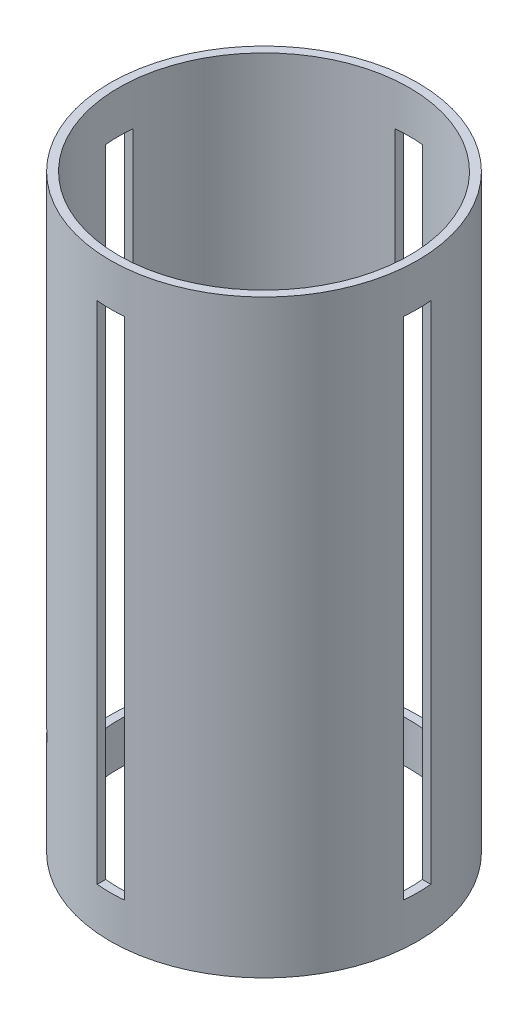
SolidWorks part; units mm, degrees
ref_plane "Front Plane" through (0, 0, 0) normal (0, 0, 1) x (1, 0, 0)
ref_plane "Top Plane" through (0, 0, 0) normal (0, 1, 0) x (1, 0, 0)
ref_plane "Right Plane" through (0, 0, 0) normal (1, 0, 0) x (0, 0, -1)
ref_axis "Axis1" through (0, 125, 0) along (0, -1, 0)
sketch "Sketch1" plane through (0, 0, 0) normal (0, 1, 0) x (1, 0, 0)
  circle A0 centre (0, 0) radius 34.5
  circle A1 centre (0, 0) radius 36.5
  dimension "D1" = 69
  dimension "D2" = 2
extrude "Boss-Extrude1" add sketch "Sketch1" along normal blind 140
sketch "Sketch3" plane through (0, 0, 0) normal (0, 0, 1) x (1, 0, 0)
  line L0 (0, 10) -> (0, 0) construction
  line L1 (-3.25, 130) -> (3.25, 130)
  line L2 (-3.25, 130) -> (-3.25, 10)
  line L3 (-3.25, 10) -> (3.25, 10)
  line L4 (3.25, 130) -> (3.25, 10)
  dimension "D1" = 120
  dimension "D2" = 10
  dimension "D3" = 6.5
extrude "Cut-Extrude1" cut sketch "Sketch3" against normal through all both and the other way through all
pattern_circular "CirPattern1" count 2 every 90 about axis through (0, 125, 0) along (0, -1, 0) of "Cut-Extrude1"
ref_plane "Plane1" through (0, 0, 0) normal (-0.7071, 0, 0.7071) x (0.7071, 0, 0.7071)
sketch "Sketch4" plane through (0, 0, 0) normal (-0.7071, 0, 0.7071) x (0.7071, 0, 0.7071)
  line L0 (0, 125) -> (0, 15) construction
  circle A0 centre (0, 25) radius 2
  dimension "D2" = 4
  dimension "D1" = 25
extrude "Cut-Extrude2" cut sketch "Sketch4" along normal through all
